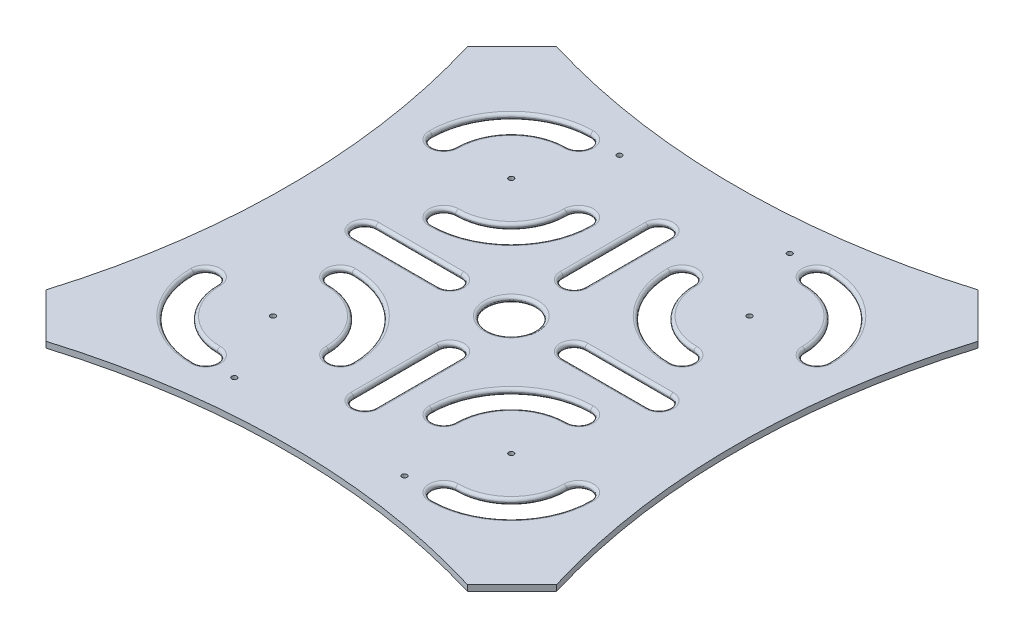
SolidWorks part; units mm, degrees
material "ABS"
ref_plane "Ön Düzlem" through (0, 0, 0) normal (0, 0, 1) x (1, 0, 0)
ref_plane "Üst Düzlem" through (0, 0, 0) normal (0, 1, 0) x (1, 0, 0)
ref_plane "Sağ Düzlem" through (0, 0, 0) normal (1, 0, 0) x (0, 0, -1)
other "Kütle Merkezi"
sketch "Çizim1" plane through (0, 0, 0) normal (0, 0, 1) x (1, 0, 0)
  line L0 (0, 0) -> (300, 0)
  line L1 (0, 0) -> (0, 3.5)
  line L2 (0, 3.5) -> (300, 3.5)
  line L3 (300, 3.5) -> (300, 0)
extrude "Yükseklik-Ekstrüzyon1" add sketch "Çizim1" against normal blind 300
sketch "Çizim2" plane through (0, 3.5, 0) normal (0, 1, 0) x (1, 0, 0)
  line L1 (0, 273.837) -> (26.163, 300)
  line L2 (0, 300) -> (0, 0) construction
  line L9 (300, 300) -> (0, 300) construction
  line L15 (0, 273.837) -> (0, 300)
  line L16 (0, 300) -> (26.163, 300)
  line L17 (273.837, 0) -> (300, 26.163)
  line L18 (273.837, 300) -> (300, 273.837)
  line L19 (300, 300) -> (300, 0) construction
  line L20 (0, 26.163) -> (26.163, 0)
  line L21 (300, 273.837) -> (300, 300)
  line L22 (300, 300) -> (273.837, 300)
  line L23 (300, 26.163) -> (300, 0)
  line L24 (300, 0) -> (273.837, 0)
  line L25 (0, 26.163) -> (0, 0)
  line L26 (0, 0) -> (26.163, 0)
  dimension "D1" = 37
  dimension "D2" = 45
  dimension "D3" = 45
  dimension "D4" = 37
  dimension "D5" = 45
  dimension "D6" = 45
sketch "Çizim3" plane through (0, 3.5, 0) normal (0, 1, 0) x (1, 0, 0)
  point P3 (150, 150)
  point P18 (149.9681, 149.9681)
sketch "Çizim8" plane through (0, 3.5, 0) normal (0, 1, 0) x (1, 0, 0)
  line L0 (186.5019, 150) -> (236.5019, 150) construction
  line L1 (186.5019, 156.4943) -> (236.5019, 156.4943)
  line L2 (150, 186.5019) -> (150, 236.5019) construction
  line L3 (143.5057, 186.5019) -> (143.5057, 236.5019)
  line L4 (156.4943, 186.5019) -> (156.4943, 236.5019)
  line L5 (186.5019, 143.5057) -> (236.5019, 143.5057)
  line L6 (150, 113.4981) -> (150, 63.4981) construction
  line L7 (156.4943, 113.4981) -> (156.4943, 63.4981)
  line L8 (143.5057, 113.4981) -> (143.5057, 63.4981)
  line L9 (113.4981, 150) -> (63.4981, 150) construction
  line L10 (113.4981, 143.5057) -> (63.4981, 143.5057)
  line L11 (113.4981, 156.4943) -> (63.4981, 156.4943)
  arc A1 (143.5057, 186.5019) -> (156.4943, 186.5019) centre (150, 186.5019) ccw
  arc A2 (156.4943, 236.5019) -> (143.5057, 236.5019) centre (150, 236.5019) ccw
  arc A4 (186.5019, 156.4943) -> (186.5019, 143.5057) centre (186.5019, 150) ccw
  arc A5 (236.5019, 143.5057) -> (236.5019, 156.4943) centre (236.5019, 150) ccw
  arc A6 (156.4943, 113.4981) -> (143.5057, 113.4981) centre (150, 113.4981) ccw
  arc A7 (143.5057, 63.4981) -> (156.4943, 63.4981) centre (150, 63.4981) ccw
  arc A8 (113.4981, 143.5057) -> (113.4981, 156.4943) centre (113.4981, 150) ccw
  arc A9 (63.4981, 156.4943) -> (63.4981, 143.5057) centre (63.4981, 150) ccw
  point P5 (211.5019, 150)
  point P9 (150, 211.5019)
  point P18 (150, 88.4981)
  point P25 (88.4981, 150)
  point P31 (150, 150)
  dimension "D1" = 4
extrude "Kes-Ekstrüzyon5" cut sketch "Çizim8" against normal blind 10
sketch "Çizim10" plane through (0, 3.5, 0) normal (0, 1, 0) x (1, 0, 0)
  circle A0 centre (150, 149.5828) radius 14
  circle A1 centre (80, 219.5828) radius 1.5
  circle A2 centre (220, 219.5828) radius 1.5
  circle A3 centre (220, 79.5828) radius 1.5
  circle A4 centre (80, 79.5828) radius 1.5
  point P72 (150, 149.5828)
  point P73 (101.2132, 100.796)
extrude "Kes-Ekstrüzyon6" cut sketch "Çizim10" against normal blind 10
sketch "Çizim13" plane through (0, 3.5, 0) normal (0, 1, 0) x (1, 0, 0)
  arc A6 (119.6542, 219.5828) -> (80, 179.9286) centre (80, 219.5828) cw construction
  arc A7 (80, 172.9978) -> (126.585, 219.5828) centre (80, 219.5828) ccw
  arc A8 (80, 186.8594) -> (112.7234, 219.5828) centre (80, 219.5828) ccw
  arc A9 (80, 186.8594) -> (80, 172.9978) centre (80, 179.9286) ccw
  arc A10 (126.585, 219.5828) -> (112.7234, 219.5828) centre (119.6542, 219.5828) ccw
  arc A11 (80, 259.237) -> (40.3458, 219.5828) centre (80, 219.5828) ccw construction
  arc A12 (33.415, 219.5828) -> (80, 266.1678) centre (80, 219.5828) cw
  arc A13 (47.2766, 219.5828) -> (80, 252.3062) centre (80, 219.5828) cw
  arc A14 (47.2766, 219.5828) -> (33.415, 219.5828) centre (40.3458, 219.5828) cw
  arc A15 (80, 266.1678) -> (80, 252.3062) centre (80, 259.237) cw
  arc A17 (180.3458, 219.5828) -> (220, 179.9286) centre (220, 219.5828) ccw construction
  arc A18 (220, 172.9978) -> (173.415, 219.5828) centre (220, 219.5828) cw
  arc A19 (220, 186.8594) -> (187.2766, 219.5828) centre (220, 219.5828) cw
  arc A20 (220, 186.8594) -> (220, 172.9978) centre (220, 179.9286) cw
  arc A21 (173.415, 219.5828) -> (187.2766, 219.5828) centre (180.3458, 219.5828) cw
  arc A22 (220, 259.237) -> (259.6542, 219.5828) centre (220, 219.5828) cw construction
  arc A23 (266.585, 219.5828) -> (220, 266.1678) centre (220, 219.5828) ccw
  arc A24 (252.7234, 219.5828) -> (220, 252.3062) centre (220, 219.5828) ccw
  arc A25 (252.7234, 219.5828) -> (266.585, 219.5828) centre (259.6542, 219.5828) ccw
  arc A26 (220, 266.1678) -> (220, 252.3062) centre (220, 259.237) ccw
  arc A27 (80, 39.9286) -> (40.3458, 79.5828) centre (80, 79.5828) cw construction
  arc A28 (33.415, 79.5828) -> (80, 32.9978) centre (80, 79.5828) ccw
  arc A29 (47.2766, 79.5828) -> (80, 46.8594) centre (80, 79.5828) ccw
  arc A30 (47.2766, 79.5828) -> (33.415, 79.5828) centre (40.3458, 79.5828) ccw
  arc A31 (80, 32.9978) -> (80, 46.8594) centre (80, 39.9286) ccw
  arc A32 (119.6542, 79.5828) -> (80, 119.237) centre (80, 79.5828) ccw construction
  arc A33 (80, 126.1678) -> (126.585, 79.5828) centre (80, 79.5828) cw
  arc A34 (80, 112.3062) -> (112.7234, 79.5828) centre (80, 79.5828) cw
  arc A35 (80, 112.3062) -> (80, 126.1678) centre (80, 119.237) cw
  arc A36 (126.585, 79.5828) -> (112.7234, 79.5828) centre (119.6542, 79.5828) cw
  arc A37 (180.3458, 79.5828) -> (220, 119.237) centre (220, 79.5828) cw construction
  arc A38 (220, 126.1678) -> (173.415, 79.5828) centre (220, 79.5828) ccw
  arc A39 (220, 112.3062) -> (187.2766, 79.5828) centre (220, 79.5828) ccw
  arc A40 (220, 112.3062) -> (220, 126.1678) centre (220, 119.237) ccw
  arc A41 (173.415, 79.5828) -> (187.2766, 79.5828) centre (180.3458, 79.5828) ccw
  arc A42 (220, 39.9286) -> (259.6542, 79.5828) centre (220, 79.5828) ccw construction
  arc A43 (266.585, 79.5828) -> (220, 32.9978) centre (220, 79.5828) cw
  arc A44 (252.7234, 79.5828) -> (220, 46.8594) centre (220, 79.5828) cw
  arc A45 (252.7234, 79.5828) -> (266.585, 79.5828) centre (259.6542, 79.5828) cw
  arc A46 (220, 32.9978) -> (220, 46.8594) centre (220, 39.9286) cw
  point P3 (108.0397, 191.5431)
  point P24 (51.9603, 247.6226)
  point P36 (191.9603, 191.5431)
  point P44 (248.0397, 247.6226)
  point P52 (51.9603, 51.5431)
  point P60 (108.0397, 107.6226)
  point P68 (191.9603, 107.6226)
  point P76 (248.0397, 51.5431)
extrude "Kes-Ekstrüzyon8" cut sketch "Çizim13" against normal blind 10
extrude "Kes-Ekstrüzyon9" cut sketch "Çizim2" against normal blind 10
sketch "Çizim16" plane through (0, 3.5, 0) normal (0, 1, 0) x (1, 0, 0)
  line L0 (26.163, 0) -> (273.837, 0)
  line L2 (300, 26.163) -> (300, 273.837)
  line L4 (273.837, 300) -> (26.163, 300)
  line L6 (0, 273.837) -> (0, 26.163)
  arc A0 (26.163, 0) -> (273.837, 0) centre (150, -407.8574) cw
  arc A1 (0, 273.837) -> (0, 26.163) centre (-407.8574, 150) cw
  arc A2 (273.837, 300) -> (26.163, 300) centre (150, 707.8574) cw
  arc A3 (300, 26.163) -> (300, 273.837) centre (707.8574, 150) cw
  point P33 (150, 150)
  dimension "D1" = 4
extrude "Kes-Ekstrüzyon10" cut sketch "Çizim16" against normal blind 10
fillet "Radyus1" radius 1.75 49 edges at (143.5057, 3.5, -211.5019) (150, 3.5, -242.9961) (156.4943, 3.5, -211.5019) (47.0594, 3.5, -252.5234) (86.9308, 3.5, -259.237) (56.8611, 3.5, -242.7218) (213.0692, 3.5, -259.237) (252.9406, 3.5, -252.5234) (259.6542, 3.5, -212.652) (180.3458, 3.5, -226.5136) (196.8611, 3.5, -196.4439) (226.9308, 3.5, -179.9286) (180.0076, 3.5, -150) (211.5019, 3.5, -156.4943) (242.9961, 3.5, -150) (57.0039, 3.5, -150) (88.4981, 3.5, -156.4943) (119.9924, 3.5, -150) (103.1389, 3.5, -196.4439) (119.6542, 3.5, -226.5136) (112.9406, 3.5, -186.6423) (40.3458, 3.5, -86.5136) (56.8611, 3.5, -56.4439) (86.9308, 3.5, -39.9286) (103.1389, 3.5, -102.7218) (73.0692, 3.5, -119.237) (112.9406, 3.5, -112.5234) (143.5057, 3.5, -88.4981) (150, 3.5, -119.9924) (156.4943, 3.5, -88.4981) (259.6542, 3.5, -86.5136) (252.9406, 3.5, -46.6423) (213.0692, 3.5, -39.9286) (187.0594, 3.5, -112.5234) (226.9308, 3.5, -119.237) (196.8611, 3.5, -102.7218) (150, 3.5, -180.0076) (40.3458, 3.5, -212.652) (243.1389, 3.5, -242.7218) (187.0594, 3.5, -186.6423) (150, 3.5, -135.5828) (211.5019, 3.5, -143.5057) (88.4981, 3.5, -143.5057) (73.0692, 3.5, -179.9286) (47.0594, 3.5, -46.6423) (119.6542, 3.5, -72.652) (150, 3.5, -57.0039) (243.1389, 3.5, -56.4439) (180.3458, 3.5, -72.652)
fillet "Radyus2" radius 1.75 49 edges at (156.4943, 0, -211.5019) (150, 0, -242.9961) (143.5057, 0, -211.5019) (259.6542, 0, -212.652) (252.9406, 0, -252.5234) (213.0692, 0, -259.237) (86.9308, 0, -259.237) (47.0594, 0, -252.5234) (40.3458, 0, -212.652) (119.6542, 0, -226.5136) (103.1389, 0, -196.4439) (73.0692, 0, -179.9286) (119.9924, 0, -150) (88.4981, 0, -156.4943) (57.0039, 0, -150) (242.9961, 0, -150) (211.5019, 0, -156.4943) (180.0076, 0, -150) (226.9308, 0, -179.9286) (196.8611, 0, -196.4439) (180.3458, 0, -226.5136) (259.6542, 0, -86.5136) (243.1389, 0, -56.4439) (213.0692, 0, -39.9286) (196.8611, 0, -102.7218) (226.9308, 0, -119.237) (187.0594, 0, -112.5234) (156.4943, 0, -88.4981) (150, 0, -119.9924) (143.5057, 0, -88.4981) (112.9406, 0, -112.5234) (73.0692, 0, -119.237) (103.1389, 0, -102.7218) (86.9308, 0, -39.9286) (56.8611, 0, -56.4439) (40.3458, 0, -86.5136) (150, 0, -180.0076) (243.1389, 0, -242.7218) (56.8611, 0, -242.7218) (112.9406, 0, -186.6423) (88.4981, 0, -143.5057) (150, 0, -163.5828) (211.5019, 0, -143.5057) (187.0594, 0, -186.6423) (252.9406, 0, -46.6423) (180.3458, 0, -72.652) (150, 0, -57.0039) (119.6542, 0, -72.652) (47.0594, 0, -46.6423)
scale "Ölçek1" scale about centroid uniform scaling yes scale factor 0.5
sketch "Çizim17" plane through (0, 0.875, 0) normal (0, -1, 0) x (-1, 0, 0)
  line L2 (-122.5, 215.6205) -> (-177.5, 215.6205)
  line L3 (-122.5, 93.6059) -> (-122.5, 102.6059)
  line L4 (-122.5, 102.6059) -> (-177.5, 102.6059)
  line L5 (-177.5, 102.6059) -> (-177.5, 84.6059)
  line L6 (-177.5, 84.6059) -> (-122.5, 84.6059)
  line L7 (-122.5, 84.6059) -> (-122.5, 93.6059)
  line L8 (-122.5, 215.6205) -> (-122.5, 197.6205)
  line L9 (-122.5, 197.6205) -> (-177.5, 197.6205)
  line L10 (-177.5, 215.6205) -> (-177.5, 197.6205)
  line L11 (-150, 197.6205) -> (-150, 215.6205) construction
  line L12 (-122.5, 206.6205) -> (-177.5, 206.6205) construction
  circle A2 centre (-125, 93.4403) radius 0.75
  circle A3 centre (-175, 93.4403) radius 0.75
  circle A9 centre (-125, 206.6205) radius 0.75
  circle A10 centre (-175, 206.6205) radius 0.75
  point P13 (-150, 93.4403)
  point P18 (-150, 206.6205)
  point P28 (-150, 206.6205)
  dimension "D1" = 18
  dimension "D2" = 55
extrude "Kes-Ekstrüzyon12" cut sketch "Çizim17" against normal blind 10 contours A9 | A10 | A2 | A3
